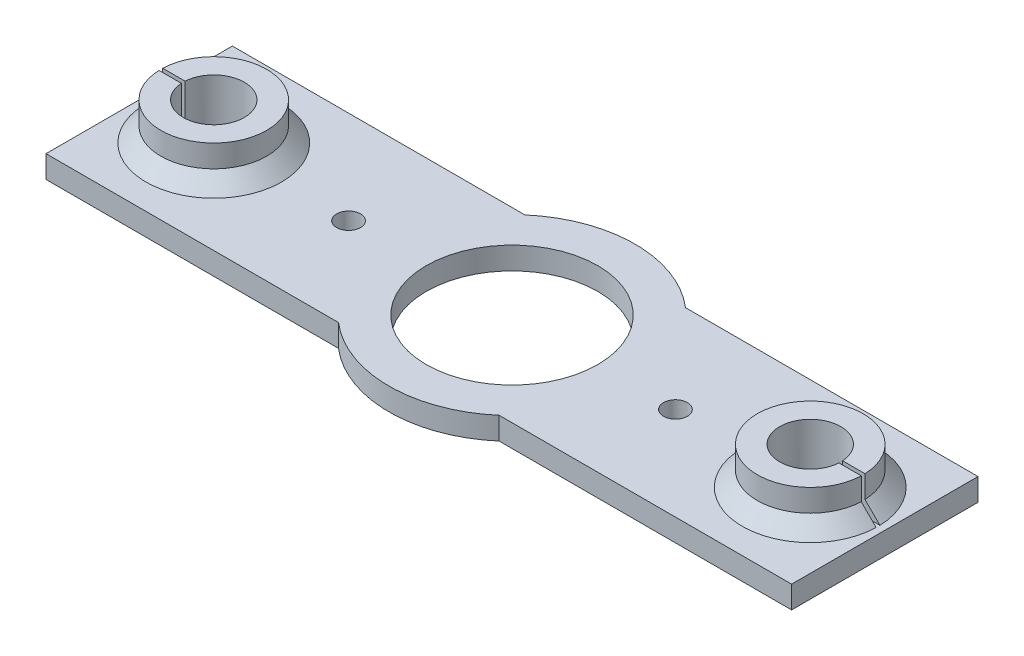
SolidWorks part; units mm, degrees
ref_plane "Front Plane" through (0, 0, 0) normal (0, 0, 1) x (1, 0, 0)
ref_plane "Top Plane" through (0, 0, 0) normal (0, 1, 0) x (1, 0, 0)
ref_plane "Right Plane" through (0, 0, 0) normal (1, 0, 0) x (0, 0, -1)
sketch "Sketch1" plane through (0, 0, 0) normal (0, 1, 0) x (1, 0, 0)
  line L0 (0, 18.2751) -> (0, -23.7638) construction
  line L1 (-40.7915, 0) -> (38.5461, 0) construction
  line L3 (50, -12.5) -> (-50, -12.5)
  line L4 (50, -12.5) -> (50, 12.5)
  line L5 (50, 12.5) -> (-50, 12.5)
  line L6 (-50, -12.5) -> (-50, 12.5)
  line L7 (50, -12.5) -> (-50, 12.5) construction
  line L8 (50, 12.5) -> (-50, -12.5) construction
  circle A0 centre (-40, 0) radius 4.1
  circle A1 centre (40, 0) radius 4.1
  circle A2 centre (-21.92, 0) radius 1.6
  circle A3 centre (21.92, 0) radius 1.6
  circle A4 centre (0, 0) radius 11.5
  circle A5 centre (0, 0) radius 16.5
  point P7 (0, 0)
  dimension "D1" = 8.2
  dimension "D2" = 80
  dimension "D5" = 3.2
  dimension "D6" = 43.84
  dimension "D7" = 23
  dimension "D8" = 5
  dimension "D3" = 25
  dimension "D4" = 100
extrude "Boss-Extrude1" add sketch "Sketch1" along normal blind 3 contours A5 L5 L6 L3 A0 A2 | L3 A5 L5 A4 | L5 A5 | A5 L3 L4 L5 A3 A1 | L3 A5 region at (31.9432, 0, 0) region at (0, 0, 14.1179) region at (0, 0, 12.086) region at (-31.9432, 0, 0) region at (0, 0, -14.1179)
sketch "Sketch2" plane through (0, 3, 0) normal (0, 1, 0) x (1, 0, 0)
  line L0 (0, 16.5) -> (0, -16.5) construction
  line L1 (0, 0) -> (-47.0975, 0) construction
  line L2 (-44.0899, 0.25) -> (-47.0931, 0.25)
  line L3 (-44.0899, -0.25) -> (-47.0931, -0.25)
  line L4 (44.0899, 0.25) -> (47.0931, 0.25)
  line L5 (44.0899, -0.25) -> (47.0931, -0.25)
  circle A0 centre (-40, 0) radius 4.0975
  circle A1 centre (-40, 0) radius 7.0975
  arc A2 (10.7703, 12.5) -> (-10.7703, 12.5) centre (0, 0) ccw construction
  arc A3 (-10.7703, -12.5) -> (10.7703, -12.5) centre (0, 0) ccw construction
  circle A4 centre (40, 0) radius 4.0975
  circle A5 centre (40, 0) radius 7.0975
  circle M13 centre (-40, 0) radius 4.1
  circle M17 centre (40, 0) radius 4.1
  dimension "D1" = 3
  dimension "D3" = 8.1951
  dimension "D2" = 0.5
extrude "Boss-Extrude2" add sketch "Sketch2" along normal blind 5 contours L3 A1 L2 M13 | A5 L5 L4 M17 region at (-45.5928, 3, -0.4507) region at (35.6993, 3, 0)
chamfer "Chamfer1" distance 2 angle 45 2 edges at (32.9025, 3, 0) (-32.9025, 3, 0)
